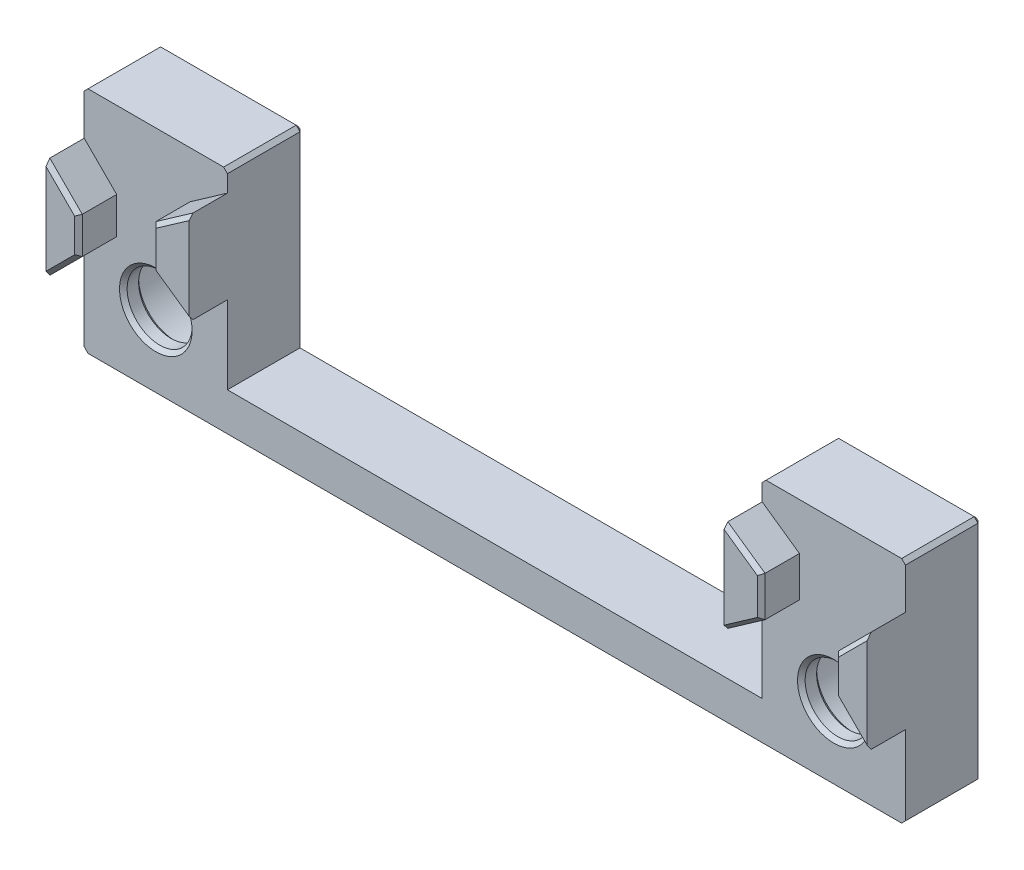
SolidWorks part; units mm, degrees
ref_plane "Front" through (0, 0, 0) normal (0, 0, 1) x (1, 0, 0)
ref_plane "Top" through (0, 0, 0) normal (0, 1, 0) x (1, 0, 0)
ref_plane "Right" through (0, 0, 0) normal (1, 0, 0) x (0, 0, -1)
sketch "Sketch1" plane through (0, 0, 0) normal (0, 0, 1) x (1, 0, 0)
  line L0 (-21.3, -6) -> (21.3, -6)
  line L5 (21.5, -5.8) -> (21.5, 5.8)
  line L6 (21.3, 6) -> (14.2, 6)
  line L7 (14, 5.8) -> (14, -4)
  line L8 (14, -4) -> (-14, -4)
  line L9 (-14, -4) -> (-14, 5.8)
  line L10 (-14.2, 6) -> (-21.3, 6)
  line L11 (-21.5, 5.8) -> (-21.5, -5.8)
  line L12 (21.5, 5.8) -> (21.5, -5.8) construction
  line L13 (21.3, 6) -> (14, 6) construction
  line L14 (21.3, -6) -> (-21.3, -6) construction
  line L15 (21.5, 5.8) -> (21.3, 6)
  line L16 (-14, 6) -> (-21.3, 6) construction
  line L17 (-21.5, 5.8) -> (-21.5, -5.8) construction
  line L18 (14.2, 6) -> (14, 5.8)
  line L19 (21.3, -6) -> (21.5, -5.8)
  line L20 (-21.5, -5.8) -> (-21.3, -6)
  line L21 (-21.3, 6) -> (-21.5, 5.8)
  line L22 (-14, 5.8) -> (-14.2, 6)
  point P0 (-21.5, -6)
  point P1 (21.5, -6)
  point P2 (21.5, 6)
  point P4 (14, 6)
  point P6 (-21.5, 6)
  point P13 (-14, 6)
  dimension "D1" = 45
  dimension "D3" = 45
  dimension "D6" = 0.2
  dimension "D5" = 45
  dimension "D7" = 45
  dimension "D12" = 0.2
  dimension "D8" = 45
  dimension "D11" = 0.2
  dimension "D9" = 0.2
  dimension "D10" = 45
  dimension "D2" = 0.2
  dimension "D4" = 0.2
extrude "Boss-Extrude1" add sketch "Sketch1" against normal blind 4
sketch "Sketch3" plane through (0, 0, 0) normal (0, 0, 1) x (1, 0, 0)
  line L1 (13.75, -0.0929) -> (15.95, 1.4475) construction
  line L7 (15.95, 1.4475) -> (15.95, 3.5525) construction
  line L8 (15.95, 3.5525) -> (13.75, 5.0929) construction
  line L9 (13.75, 5.0929) -> (11.55, 3.5525) construction
  line L10 (11.55, 3.5525) -> (11.55, 1.4475) construction
  line L11 (11.55, 1.4475) -> (13.75, -0.0929) construction
  line L12 (16.1, 1.3694) -> (16.1, 3.6306)
  line L13 (16.1, 3.6306) -> (13.75, 5.276)
  line L14 (13.75, 5.276) -> (11.4, 3.6306)
  line L16 (11.4, 3.6306) -> (11.4, 1.3694)
  line L30 (11.4, 1.3694) -> (13.75, -0.276)
  line L32 (13.75, -0.276) -> (16.1, 1.3694)
  line L36 (16.1, 1.3694) -> (16.1, 3.6306) construction
  line L46 (16.1, 3.6306) -> (13.75, 5.276) construction
  line L47 (13.75, 5.276) -> (11.4, 3.6306) construction
  line L48 (11.4, 3.6306) -> (11.4, 1.3694) construction
  line L49 (11.4, 1.3694) -> (13.75, -0.276) construction
  line L50 (13.75, -0.276) -> (16.1, 1.3694) construction
  line L51 (14, 4.9179) -> (14, 0.0821)
  line L52 (14, 0.0821) -> (15.95, 1.4475)
  line L53 (15.95, 1.4475) -> (15.95, 3.5525)
  line L54 (15.95, 3.5525) -> (14, 4.9179)
  line L55 (14, 6) -> (14, 5.101) construction
  line M6 (14, 5.8) -> (14, -4)
  dimension "D1" = 0
  dimension "D2" = 0.15
extrude "Slot Aligner" add sketch "Sketch3" along normal blind 2 contours L53 L54 L52 M6 region at (14.8471, 2.5, 0)
mirror "Mirror3" about plane through (0, 0, 0) normal (1, 0, 0) of "Slot Aligner"
sketch "Sketch4" plane through (0, 0, 0) normal (0, 0, -1) x (-1, 0, 0)
  line L8 (-19.8, 1.9586) -> (-21.4, 3.5586)
  line L10 (-21.4, -1.5586) -> (-19.8, 0.0414)
  line L11 (-19.8, 0.0414) -> (-19.8, 1.9586)
  line L21 (-21.5, -1.8) -> (-19.7, 0)
  line L25 (-19.7, 0) -> (-19.7, 2)
  line L26 (-19.7, 2) -> (-21.5, 3.8)
  line L27 (-21.5, 3.8) -> (-21.5, -1.8)
  line L28 (-21.5, -1.8) -> (-19.7, 0) construction
  line L29 (-19.7, 0) -> (-19.7, 2) construction
  line L30 (-19.7, 2) -> (-21.5, 3.8) construction
  line L31 (-21.5, 3.8) -> (-21.5, -1.8) construction
  line L32 (-21.4, 3.5586) -> (-21.5, 3.6586)
  line L33 (-21.5, 3.6586) -> (-21.5, -1.6586)
  line L34 (-21.5, -1.6586) -> (-21.4, -1.5586)
  line L36 (-21.4, 3.5586) -> (-21.4, -1.5586) construction
  dimension "D1" = 0
  dimension "D2" = 0.1
extrude "Aligner" add sketch "Sketch4" against normal blind 2
mirror "Aligners" about plane through (0, 0, 0) normal (1, 0, 0) of "Aligner"
chamfer "Deburs" distance 0.2 angle 45 26 edges at (14, 0.9, -4) (14.1, 5.9, -4) (17.75, 6, -4) (21.4, 5.9, -4) (21.5, 0, -4) (21.4, -5.9, -4) (0, -6, -4) (-21.4, -5.9, -4) (-21.5, 0, -4) (-21.4, 5.9, -4) (-17.75, 6, -4) (-14.1, 5.9, -4) (-14, 0.9, -4) (0, -4, -4) (20.65, -0.8086, 2) (20.65, 2.8086, 2) (19.8, 1, 2) (14.975, 4.2352, 2) (15.95, 2.5, 2) (14.975, 0.7648, 2) (-14.975, 4.2352, 2) (-15.95, 2.5, 2) (-14.975, 0.7648, 2) (-20.65, 2.8086, 2) (-19.8, 1, 2) (-20.65, -0.8086, 2)
sketch "Sketch5" plane through (0, 0, -4) normal (0, 0, -1) x (-1, 0, 0)
  point P0 (-17.75, -2.25)
  point P1 (17.75, -2.25)
hole_wizard "CBORE for M3 SHCS1" positions "Sketch5" profile "Sketch6" counterbore size "M3" standard "ANSI Metric" end condition through all
sketch "Sketch6" plane through (17.75, -2.25, -4) normal (1, 0, 0) x (0, 1, 0)
  line L0 (0, 0) -> (0, 6)
  line L1 (0, 6) -> (1.7, 6)
  line L3 (1.7, 6) -> (1.7, 3)
  line L4 (1.7, 3) -> (3.25, 3)
  line L5 (3.25, 3) -> (3.25, 0)
  line L7 (3.25, 0) -> (0, 0)
  line L11 (0, -6.35) -> (0, 107.95) construction
  dimension "Thru Hole Dia." = 3.4
  dimension "Thru Hole Depth" = 6
  dimension "C'Bore Dia." = 6.5
  dimension "C'Bore Depth" = 3
chamfer "Chamfer1" distance 0.2 angle 45 6 edges at (-19.45, -2.25, 0) (-19.45, -2.25, -1) (16.05, -2.25, 0) (16.05, -2.25, -1) (14.5, -2.25, -4) (-21, -2.25, -4)
